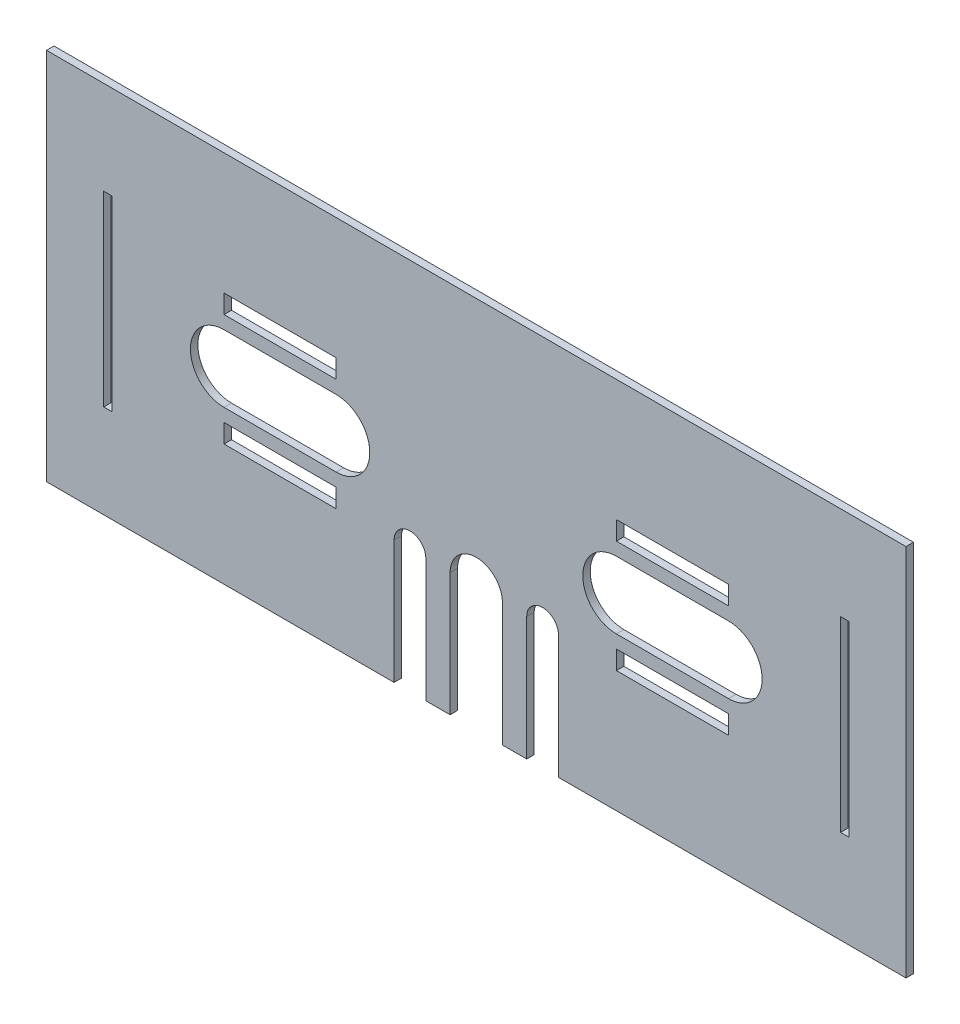
SolidWorks part; units mm, degrees
ref_plane "前视基准面" through (0, 0, 0) normal (0, 0, 1) x (1, 0, 0)
ref_plane "上视基准面" through (0, 0, 0) normal (0, 1, 0) x (1, 0, 0)
ref_plane "右视基准面" through (0, 0, 0) normal (1, 0, 0) x (0, 0, -1)
sketch "草图1" plane through (0, 0, 0) normal (0, 0, 1) x (1, 0, 0)
  line L1 (-49.0448, 20.924) -> (180.9552, 20.924)
  line L2 (-49.0448, 20.924) -> (-49.0448, -79.076)
  line L3 (-49.0448, -79.076) -> (180.9552, -79.076)
  line L4 (180.9552, 20.924) -> (180.9552, -79.076)
  dimension "D1" = 100
  dimension "D2" = 230
extrude "凸台-拉伸1" add sketch "草图1" along normal blind 2
sketch "草图3" plane through (0, 0, 0) normal (0, 0, 1) x (1, 0, 0)
  line L0 (-49.0448, 20.924) -> (-49.0448, -79.076) construction
  line L1 (-33.7448, -4.076) -> (-31.5448, -4.076)
  line L2 (-33.7448, -4.076) -> (-33.7448, -54.076)
  line L3 (-33.7448, -54.076) -> (-31.5448, -54.076)
  line L4 (-31.5448, -4.076) -> (-31.5448, -54.076)
  line L5 (-32.6448, -54.076) -> (-32.6448, -4.076) construction
  line L6 (-33.7448, -29.076) -> (-31.5448, -29.076) construction
  line L7 (180.9552, 20.924) -> (-49.0448, 20.924) construction
  line L8 (65.9552, 82.5756) -> (65.9552, 20.924) construction
  line L9 (65.9552, 20.924) -> (65.9552, -17.9618) construction
  line L10 (-56.6463, -29.076) -> (16.0347, -29.076) construction
  line L11 (16.0347, -29.076) -> (128.3085, -29.076) construction
  line L12 (-1.5448, -44.076) -> (28.4552, -44.076) construction
  line L13 (-1.5448, -11.576) -> (28.4552, -11.576)
  line L14 (-1.5448, -11.576) -> (-1.5448, -16.576)
  line L15 (-1.5448, -16.576) -> (28.4552, -16.576)
  line L16 (28.4552, -11.576) -> (28.4552, -16.576)
  line L17 (13.4552, -16.576) -> (13.4552, -11.576) construction
  line L18 (-1.5448, -14.076) -> (28.4552, -14.076) construction
  line L19 (-1.5448, -20.076) -> (28.4552, -20.076)
  line L21 (-1.5448, -38.076) -> (28.4552, -38.076)
  line L23 (13.4552, -38.076) -> (13.4552, -20.076) construction
  line L24 (-10.6742, -29.076) -> (32.0973, -29.076) construction
  line L25 (13.4552, -41.576) -> (13.4552, -46.576) construction
  line L26 (28.4552, -46.576) -> (28.4552, -41.576)
  line L27 (-1.5448, -41.576) -> (28.4552, -41.576)
  line L28 (-1.5448, -46.576) -> (-1.5448, -41.576)
  line L29 (-1.5448, -46.576) -> (28.4552, -46.576)
  line L30 (118.4552, -41.576) -> (118.4552, -46.576) construction
  line L31 (142.5847, -29.076) -> (99.8132, -29.076) construction
  line L32 (118.4552, -38.076) -> (118.4552, -20.076) construction
  line L33 (133.4552, -14.076) -> (103.4552, -14.076) construction
  line L34 (118.4552, -16.576) -> (118.4552, -11.576) construction
  line L35 (133.4552, -44.076) -> (103.4552, -44.076) construction
  line L36 (165.6552, -29.076) -> (163.4552, -29.076) construction
  line L37 (164.5552, -54.076) -> (164.5552, -4.076) construction
  line L38 (133.4552, -46.576) -> (103.4552, -46.576)
  line L39 (133.4552, -46.576) -> (133.4552, -41.576)
  line L40 (133.4552, -41.576) -> (103.4552, -41.576)
  line L41 (103.4552, -46.576) -> (103.4552, -41.576)
  line L42 (133.4552, -38.076) -> (103.4552, -38.076)
  line L43 (133.4552, -20.076) -> (103.4552, -20.076)
  line L44 (103.4552, -11.576) -> (103.4552, -16.576)
  line L45 (133.4552, -16.576) -> (103.4552, -16.576)
  line L46 (133.4552, -11.576) -> (133.4552, -16.576)
  line L47 (133.4552, -11.576) -> (103.4552, -11.576)
  line L48 (163.4552, -4.076) -> (163.4552, -54.076)
  line L49 (165.6552, -54.076) -> (163.4552, -54.076)
  line L50 (165.6552, -4.076) -> (165.6552, -54.076)
  line L51 (165.6552, -4.076) -> (163.4552, -4.076)
  line L52 (-49.0448, -79.076) -> (180.9552, -79.076) construction
  arc A0 (28.4552, -20.076) -> (28.4552, -38.076) centre (28.4552, -29.076) cw
  arc A1 (-1.5448, -20.076) -> (-1.5448, -38.076) centre (-1.5448, -29.076) ccw
  arc A2 (133.4552, -20.076) -> (133.4552, -38.076) centre (133.4552, -29.076) cw
  arc A3 (103.4552, -20.076) -> (103.4552, -38.076) centre (103.4552, -29.076) ccw
  point P26 (0, 0)
  point P27 (0, 0)
  point P28 (0, 0)
  point P38 (13.4552, -44.076)
  point P73 (118.4552, -29.076)
  point P74 (164.5552, -29.076)
  point P75 (118.4552, -14.076)
  point P76 (118.4552, -44.076)
  point P165 (13.4552, -14.076)
  point P364 (-32.6448, -29.076)
  point P526 (13.4552, -29.076)
  dimension "D9" = 9
  dimension "D10" = 9
  dimension "D3" = 50
  dimension "D4" = 2.2
  dimension "D5" = 12.5
  dimension "D6" = 5
  dimension "D7" = 37.5
  dimension "D8" = 30
  dimension "D11" = 30
  dimension "D12" = 18
  dimension "D13" = 37.5
  dimension "D14" = 16.4
  dimension "D15" = 50
extrude "切除-拉伸2" cut sketch "草图3" against normal blind 2 and the other way blind 2
sketch "草图4" plane through (0, 0, 0) normal (0, 0, 1) x (1, 0, 0)
  line L0 (-49.0448, -79.076) -> (180.9552, -79.076) construction
  line L2 (43.9552, -46.076) -> (43.9552, -79.076)
  line L3 (43.9552, -79.076) -> (52.4552, -79.076)
  line L4 (52.4552, -46.076) -> (52.4552, -79.076)
  line L5 (48.2052, -79.076) -> (48.2052, -46.076) construction
  line L6 (43.9552, -62.576) -> (52.4552, -62.576) construction
  line L7 (65.9552, 49.5064) -> (65.9552, -10.9661) construction
  line L8 (87.9552, -62.576) -> (79.4552, -62.576) construction
  line L9 (180.9552, 20.924) -> (-49.0448, 20.924) construction
  line L12 (58.9552, -46.076) -> (58.9552, -79.076)
  line L13 (58.9552, -79.076) -> (72.9552, -79.076)
  line L14 (72.9552, -46.076) -> (72.9552, -79.076)
  line L15 (65.9552, -79.076) -> (65.9552, -46.076) construction
  line L16 (58.9552, -62.576) -> (72.9552, -62.576) construction
  line L17 (83.7052, -79.076) -> (83.7052, -46.076) construction
  line L18 (79.4552, -46.076) -> (79.4552, -79.076)
  line L19 (87.9552, -79.076) -> (79.4552, -79.076)
  line L20 (87.9552, -46.076) -> (87.9552, -79.076)
  arc A0 (43.9552, -46.076) -> (52.4552, -46.076) centre (48.2052, -46.076) cw
  arc A1 (58.9552, -46.076) -> (72.9552, -46.076) centre (65.9552, -46.076) cw
  arc A2 (87.9552, -46.076) -> (79.4552, -46.076) centre (83.7052, -46.076) ccw
  point P11 (65.9552, 20.924)
  point P27 (83.7052, -62.576)
  point P155 (65.9552, -62.576)
  point P332 (48.2052, -62.576)
  dimension "D5" = 4.25
  dimension "D6" = 7
  dimension "D1" = 33
  dimension "D2" = 8.5
  dimension "D3" = 6.5
  dimension "D4" = 14
  dimension "D7" = 33
extrude "切除-拉伸3" cut sketch "草图4" against normal blind 2 and the other way blind 2
